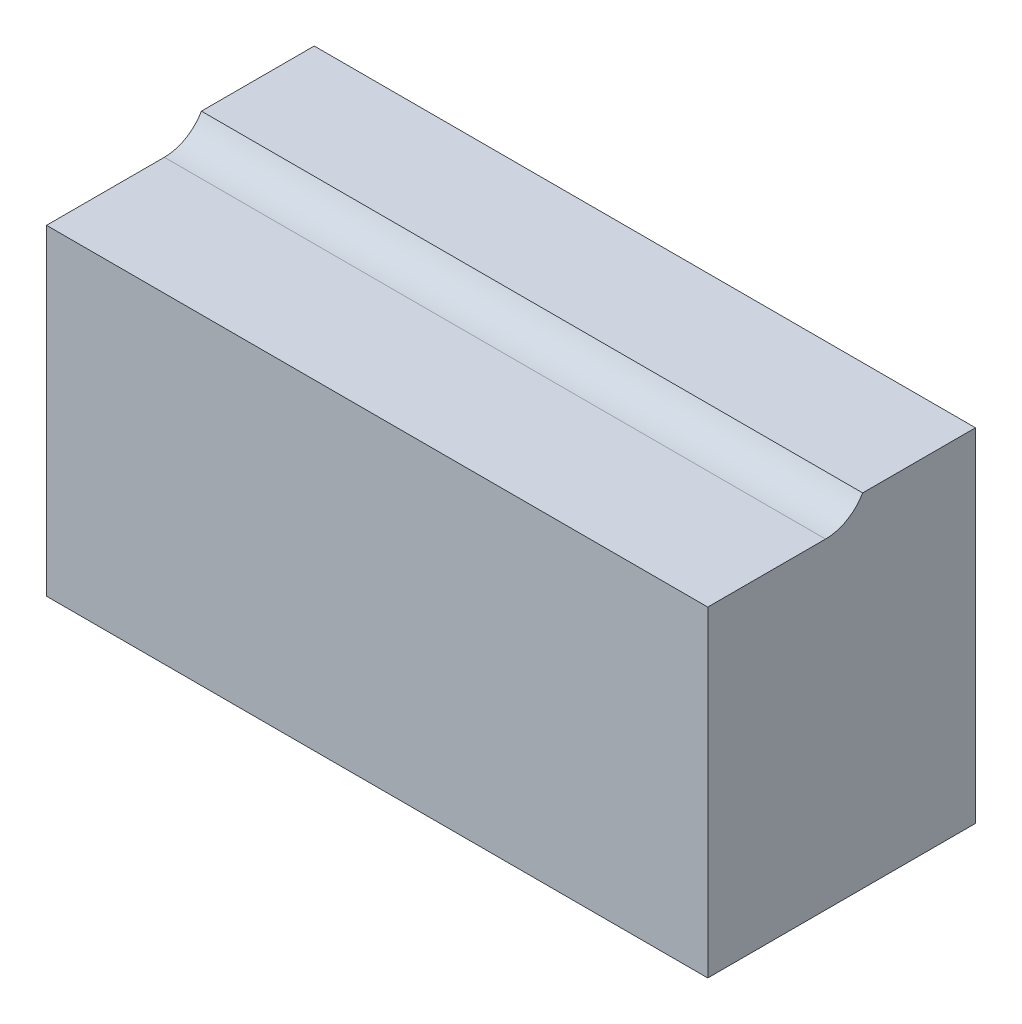
SolidWorks part; units mm, degrees
material "K110"
ref_plane "Front Plane" through (0, 0, 0) normal (0, 0, 1) x (1, 0, 0)
ref_plane "Top Plane" through (0, 0, 0) normal (0, 1, 0) x (1, 0, 0)
ref_plane "Right Plane" through (0, 0, 0) normal (1, 0, 0) x (0, 0, -1)
sketch "Sketch1" plane through (0, 0, 0) normal (0, 0, 1) x (1, 0, 0)
  line L1 (5.7154, -38) -> (67.4654, -38)
  line L2 (5.7154, -38) -> (5.7154, 0)
  line L3 (5.7154, 0) -> (67.4654, 0)
  line L4 (67.4654, -38) -> (67.4654, 0)
  dimension "D1" = 38
  dimension "D2" = 61.75
extrude "Boss-Extrude1" add sketch "Sketch1" along normal mid plane 25
sketch "Sketch2" plane through (67.4654, 0, 0) normal (1, 0, 0) x (0, 0, -1)
  line L0 (1.9641, -6) -> (12.5, -6)
  line L1 (12.5, -38) -> (12.5, 0) construction
  line L2 (12.5, -6) -> (12.5, 0)
  line L3 (12.5, 0) -> (-12.5, 0)
  line L4 (-12.5, 0) -> (-12.5, -8)
  line L5 (-12.5, -38) -> (-12.5, 0) construction
  line L6 (-12.5, -8) -> (-1.5, -8)
  line L7 (-12.5, -38) -> (12.5, -38) construction
  arc A0 (-1.5, -8) -> (-5.4392, -4.6946) centre (-1.5, -4) ccw construction
  arc A1 (-1.5, -8) -> (1.9641, -6) centre (-1.5, -4) ccw
  dimension "D1" = 32
extrude "Cut-Extrude1" cut sketch "Sketch2" against normal up to next
